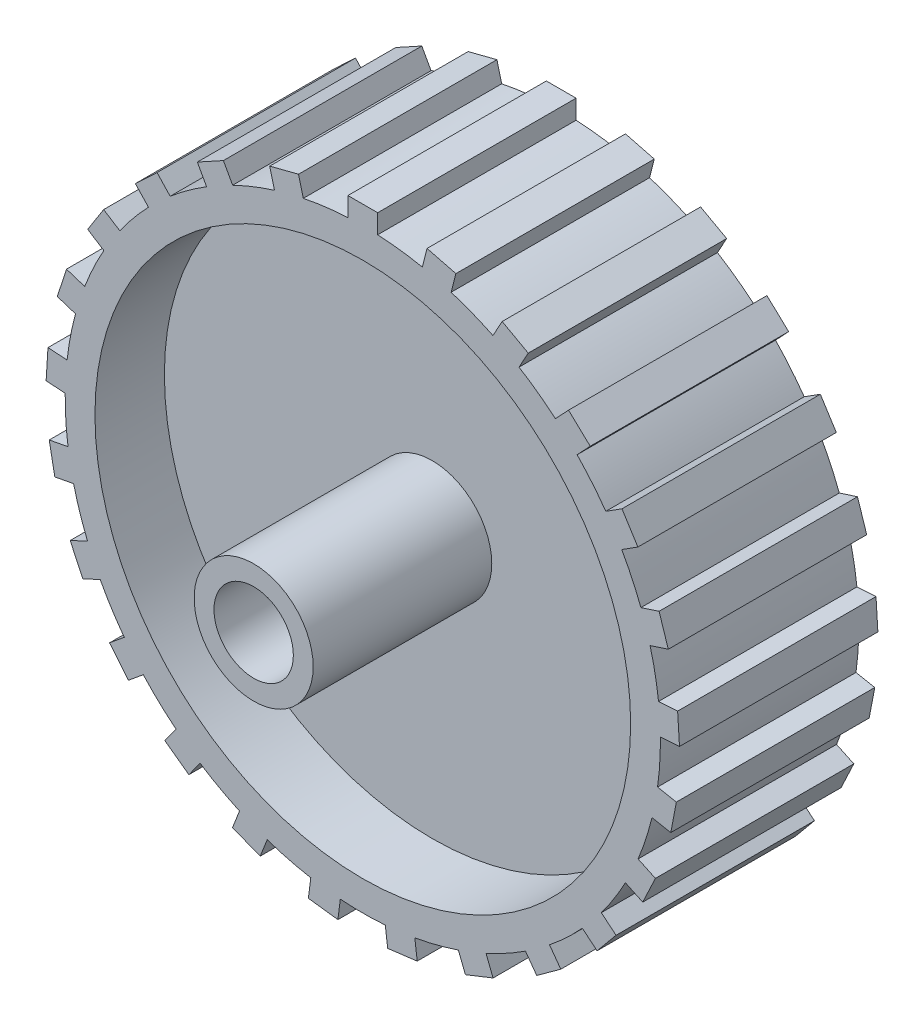
SolidWorks part; units mm, degrees
ref_plane "Front Plane" through (0, 0, 0) normal (0, 0, 1) x (1, 0, 0)
ref_plane "Top Plane" through (0, 0, 0) normal (0, 1, 0) x (1, 0, 0)
ref_plane "Right Plane" through (0, 0, 0) normal (1, 0, 0) x (0, 0, -1)
sketch "Sketch1" plane through (0, 0, 0) normal (0, 0, 1) x (1, 0, 0)
  circle A0 centre (0, 0) radius 30
  dimension "D1" = 60
extrude "Boss-Extrude1" add sketch "Sketch1" along normal blind 20
sketch "Sketch2" plane through (0, 0, 20) normal (0, 0, 1) x (1, 0, 0)
  circle A0 centre (0, 0) radius 27
  circle A1 centre (0, 0) radius 30 construction
  dimension "D1" = 3
extrude "Cut-Extrude1" cut sketch "Sketch2" against normal blind 7
sketch "Sketch3" plane through (0, 0, 0) normal (0, 0, -1) x (-1, 0, 0)
  circle A0 centre (0, 0) radius 27
  circle A1 centre (0, 0) radius 30 construction
  dimension "D1" = 3
extrude "Cut-Extrude2" cut sketch "Sketch3" against normal blind 9
sketch "Sketch4" plane through (0, 0, 13) normal (0, 0, 1) x (1, 0, 0)
  circle A0 centre (0, 0) radius 6
  circle A1 centre (0, 0) radius 4
  dimension "D1" = 12
  dimension "D2" = 8
extrude "Boss-Extrude2" add sketch "Sketch4" along normal blind 18
sketch "Sketch5" plane through (0, 0, 9) normal (0, 0, -1) x (-1, 0, 0)
  circle A0 centre (0, 0) radius 6
  dimension "D1" = 12
extrude "Boss-Extrude3" add sketch "Sketch5" along normal blind 2
sketch "Sketch6" plane through (0, 0, 31) normal (0, 0, 1) x (1, 0, 0)
  circle A0 centre (0, 0) radius 4
extrude "Cut-Extrude7" cut sketch "Sketch6" against normal blind 42
sketch "Sketch7" plane through (0, 0, 20) normal (0, 0, 1) x (1, 0, 0)
  line L0 (0, 0) -> (0, 38.0142) construction
  line L2 (-1.5, 31.8914) -> (1.5, 31.8914)
  line L3 (-1.5, 31.8914) -> (-1.5, 29.8914)
  line L4 (-1.5, 29.8914) -> (1.5, 29.8914)
  line L5 (1.5, 31.8914) -> (1.5, 29.8914)
  dimension "D2" = 2
  dimension "D1" = 3
extrude "Boss-Extrude4" add sketch "Sketch7" against normal up to surface (20 mm away) up to face at (-27, 0, 0)
pattern_circular "CirPattern1" count 25 over 360 about axis through (0, 0, 20) along (0, 0, 1) of "Boss-Extrude4"
